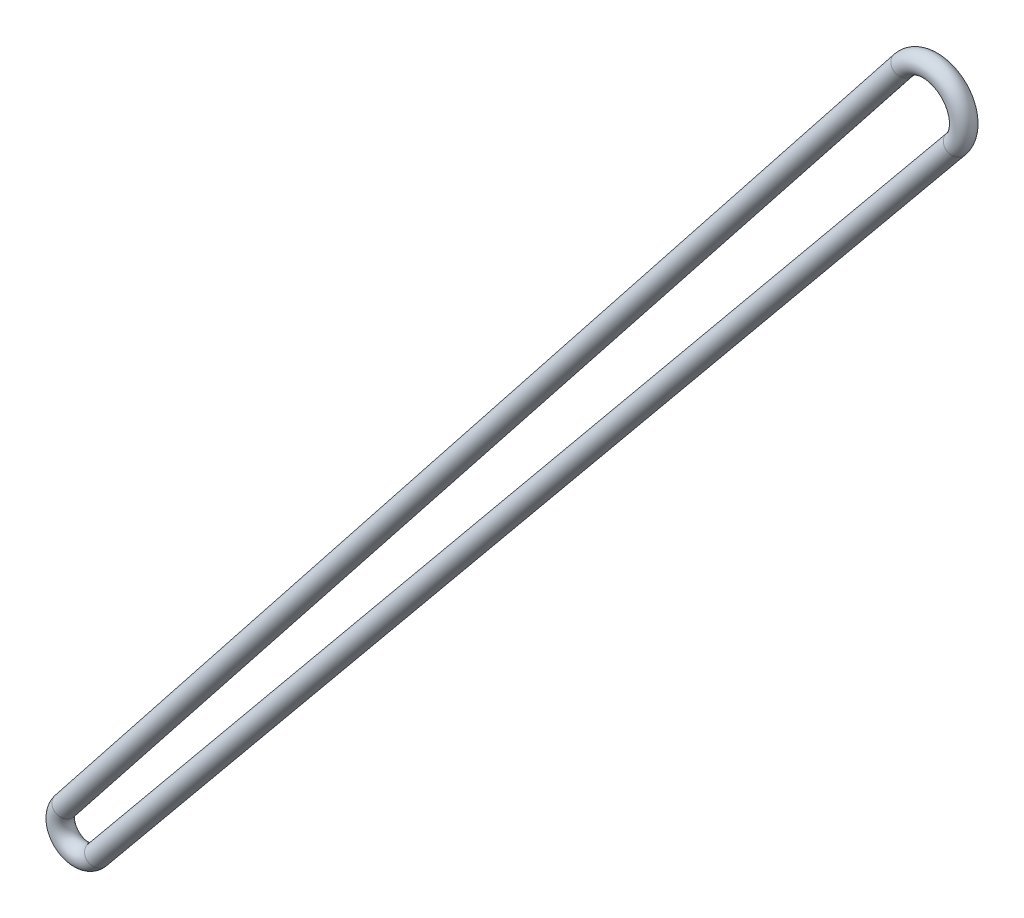
SolidWorks part; units mm, degrees
ref_plane "前视基准面" through (0, 0, 0) normal (0, 0, 1) x (1, 0, 0)
ref_plane "上视基准面" through (0, 0, 0) normal (0, 1, 0) x (1, 0, 0)
ref_plane "右视基准面" through (0, 0, 0) normal (1, 0, 0) x (0, 0, -1)
sketch "草图2" plane through (0, 0, 0) normal (0, 0, 1) x (1, 0, 0)
  line L0 (0, 0) -> (1, 0) construction
  line L1 (0, 0) -> (0, 1) construction
  line L2 (-2.5068, 1.9919) -> (122.0041, 159.4896)
  line L3 (129.7894, 153.2142) -> (2.32, -1.8988)
  arc A0 (2.32, -1.8988) -> (-2.5068, 1.9919) centre (-0.075, 0.0694) cw
  arc A1 (122.0041, 159.4896) -> (129.7894, 153.2142) centre (125.9264, 156.3887) cw
sweep "扫描19" add path "草图2" circular profile diameter 3 parameters "D3"=3
